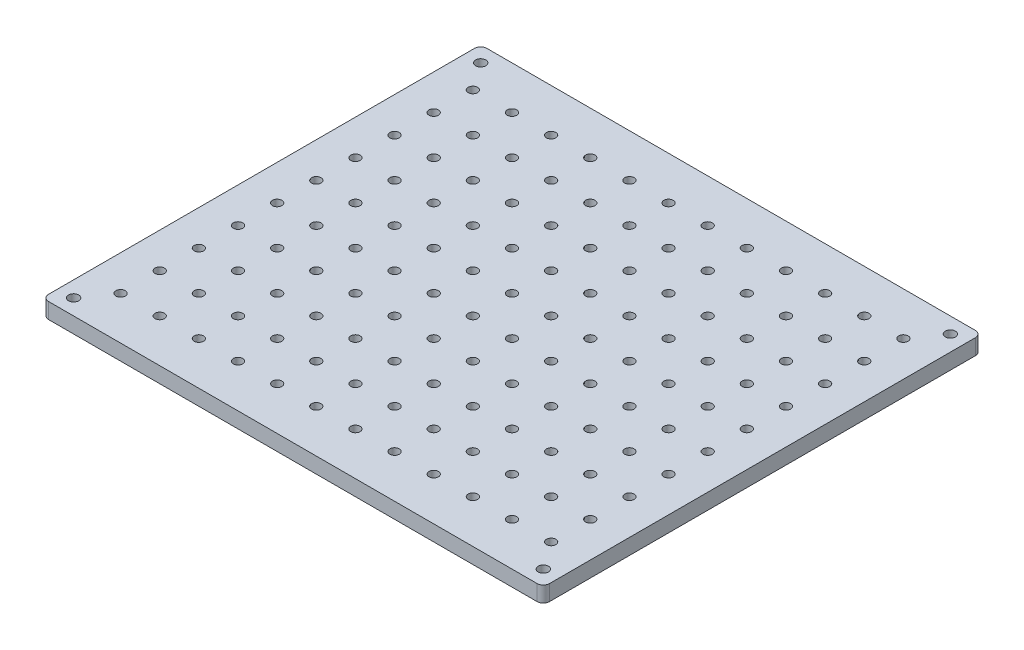
SolidWorks part; units mm, degrees
ref_plane "前视基准面" through (0, 0, 0) normal (0, 0, 1) x (1, 0, 0)
ref_plane "上视基准面" through (0, 0, 0) normal (0, 1, 0) x (1, 0, 0)
ref_plane "右视基准面" through (0, 0, 0) normal (1, 0, 0) x (0, 0, -1)
sketch "草图1" plane through (0, 0, 0) normal (0, 1, 0) x (1, 0, 0)
  line L1 (-160, -140) -> (160, -140)
  line L2 (-160, -140) -> (-160, 140)
  line L3 (-160, 140) -> (160, 140)
  line L4 (160, -140) -> (160, 140)
  line L5 (-160, -140) -> (160, 140) construction
  line L6 (-160, 140) -> (160, -140) construction
  point P0 (0, 0)
extrude "凸台-拉伸1" add sketch "草图1" along normal blind 10
sketch "草图2" plane through (0, 10, 0) normal (0, 1, 0) x (1, 0, 0)
  line L0 (-160, 140) -> (-150, 140)
  line L1 (160, 140) -> (-160, 140) construction
  line L2 (-150, 140) -> (-150, 130)
  line L3 (160, 130) -> (150, 130)
  line L4 (160, -140) -> (160, 140) construction
  line L5 (-150, -140) -> (-150, -130)
  line L6 (-160, -140) -> (160, -140) construction
  circle A0 centre (-150, 130) radius 3.25
  circle A1 centre (-150, 130) radius 2
  circle A2 centre (150, 130) radius 3.25
  circle A3 centre (150, 130) radius 2
  circle A4 centre (-150, -130) radius 3.25
  circle A5 centre (-150, -130) radius 2
  circle A6 centre (150, -130) radius 3.25
  circle A7 centre (150, -130) radius 2
  point P20 (-106.6373, 126.2998)
  point P21 (148.03, 130)
  point P24 (-152.8758, -130)
  point P27 (150, -130)
extrude "切除-拉伸1" cut sketch "草图2" against normal blind 5 contours A6 A7 | A5 A4 | A1 A0 | A3 A2 region at (-147.7669, 10, -132.2331) region at (146.8419, 10, -130) region at (-152.2331, 10, 127.7669) region at (146.8419, 10, 130)
extrude "切除-拉伸2" cut sketch "草图2<3>" against normal through all contours A1 | A3 | A7 | A5 region at (-148.6258, 10, -131.3742) region at (148.0566, 10, -130) region at (-151.3742, 10, 128.6258) region at (150, 10, 130)
sketch "草图2<3>" plane through (0, 10, 0) normal (0, 1, 0) x (1, 0, 0) same geometry as "草图2"
sketch "草图4" plane through (0, 10, 0) normal (0, 1, 0) x (1, 0, 0)
  circle A0 centre (-137.5, 112.5) radius 3
  circle A1 centre (-112.5, 112.5) radius 3
  circle A2 centre (-87.5, 112.5) radius 3
  circle A3 centre (-62.5, 112.5) radius 3
  circle A4 centre (-37.5, 112.5) radius 3
  circle A5 centre (-12.5, 112.5) radius 3
  circle A6 centre (12.5, 112.5) radius 3
  circle A7 centre (37.5, 112.5) radius 3
  circle A8 centre (62.5, 112.5) radius 3
  circle A9 centre (87.5, 112.5) radius 3
  circle A10 centre (112.5, 112.5) radius 3
  circle A11 centre (137.5, 112.5) radius 3
  circle A12 centre (-112.5, 87.5) radius 3
  circle A13 centre (-87.5, 87.5) radius 3
  circle A14 centre (-62.5, 87.5) radius 3
  circle A15 centre (-37.5, 87.5) radius 3
  circle A16 centre (-12.5, 87.5) radius 3
  circle A17 centre (12.5, 87.5) radius 3
  circle A18 centre (37.5, 87.5) radius 3
  circle A19 centre (62.5, 87.5) radius 3
  circle A20 centre (87.5, 87.5) radius 3
  circle A21 centre (112.5, 87.5) radius 3
  circle A22 centre (137.5, 87.5) radius 3
  circle A23 centre (-112.5, 62.5) radius 3
  circle A24 centre (-87.5, 62.5) radius 3
  circle A25 centre (-62.5, 62.5) radius 3
  circle A26 centre (-37.5, 62.5) radius 3
  circle A27 centre (-12.5, 62.5) radius 3
  circle A28 centre (12.5, 62.5) radius 3
  circle A29 centre (37.5, 62.5) radius 3
  circle A30 centre (62.5, 62.5) radius 3
  circle A31 centre (87.5, 62.5) radius 3
  circle A32 centre (112.5, 62.5) radius 3
  circle A33 centre (137.5, 62.5) radius 3
  circle A34 centre (-112.5, 37.5) radius 3
  circle A35 centre (-87.5, 37.5) radius 3
  circle A36 centre (-62.5, 37.5) radius 3
  circle A37 centre (-37.5, 37.5) radius 3
  circle A38 centre (-12.5, 37.5) radius 3
  circle A39 centre (12.5, 37.5) radius 3
  circle A40 centre (37.5, 37.5) radius 3
  circle A41 centre (62.5, 37.5) radius 3
  circle A42 centre (87.5, 37.5) radius 3
  circle A43 centre (112.5, 37.5) radius 3
  circle A44 centre (137.5, 37.5) radius 3
  circle A45 centre (-112.5, 12.5) radius 3
  circle A46 centre (-87.5, 12.5) radius 3
  circle A47 centre (-62.5, 12.5) radius 3
  circle A48 centre (-37.5, 12.5) radius 3
  circle A49 centre (-12.5, 12.5) radius 3
  circle A50 centre (12.5, 12.5) radius 3
  circle A51 centre (37.5, 12.5) radius 3
  circle A52 centre (62.5, 12.5) radius 3
  circle A53 centre (87.5, 12.5) radius 3
  circle A54 centre (112.5, 12.5) radius 3
  circle A55 centre (137.5, 12.5) radius 3
  circle A56 centre (-112.5, -12.5) radius 3
  circle A57 centre (-87.5, -12.5) radius 3
  circle A58 centre (-62.5, -12.5) radius 3
  circle A59 centre (-37.5, -12.5) radius 3
  circle A60 centre (-12.5, -12.5) radius 3
  circle A61 centre (12.5, -12.5) radius 3
  circle A62 centre (37.5, -12.5) radius 3
  circle A63 centre (62.5, -12.5) radius 3
  circle A64 centre (87.5, -12.5) radius 3
  circle A65 centre (112.5, -12.5) radius 3
  circle A66 centre (137.5, -12.5) radius 3
  circle A67 centre (-112.5, -37.5) radius 3
  circle A68 centre (-87.5, -37.5) radius 3
  circle A69 centre (-62.5, -37.5) radius 3
  circle A70 centre (-37.5, -37.5) radius 3
  circle A71 centre (-12.5, -37.5) radius 3
  circle A72 centre (12.5, -37.5) radius 3
  circle A73 centre (37.5, -37.5) radius 3
  circle A74 centre (62.5, -37.5) radius 3
  circle A75 centre (87.5, -37.5) radius 3
  circle A76 centre (112.5, -37.5) radius 3
  circle A77 centre (137.5, -37.5) radius 3
  circle A78 centre (-112.5, -62.5) radius 3
  circle A79 centre (-87.5, -62.5) radius 3
  circle A80 centre (-62.5, -62.5) radius 3
  circle A81 centre (-37.5, -62.5) radius 3
  circle A82 centre (-12.5, -62.5) radius 3
  circle A83 centre (12.5, -62.5) radius 3
  circle A84 centre (37.5, -62.5) radius 3
  circle A85 centre (62.5, -62.5) radius 3
  circle A86 centre (87.5, -62.5) radius 3
  circle A87 centre (112.5, -62.5) radius 3
  circle A88 centre (137.5, -62.5) radius 3
  circle A89 centre (-112.5, -87.5) radius 3
  circle A90 centre (-87.5, -87.5) radius 3
  circle A91 centre (-62.5, -87.5) radius 3
  circle A92 centre (-37.5, -87.5) radius 3
  circle A93 centre (-12.5, -87.5) radius 3
  circle A94 centre (12.5, -87.5) radius 3
  circle A95 centre (37.5, -87.5) radius 3
  circle A96 centre (62.5, -87.5) radius 3
  circle A97 centre (87.5, -87.5) radius 3
  circle A98 centre (112.5, -87.5) radius 3
  circle A99 centre (137.5, -87.5) radius 3
  circle A100 centre (-112.5, -112.5) radius 3
  circle A101 centre (-87.5, -112.5) radius 3
  circle A102 centre (-62.5, -112.5) radius 3
  circle A103 centre (-37.5, -112.5) radius 3
  circle A104 centre (-12.5, -112.5) radius 3
  circle A105 centre (12.5, -112.5) radius 3
  circle A106 centre (37.5, -112.5) radius 3
  circle A107 centre (62.5, -112.5) radius 3
  circle A108 centre (87.5, -112.5) radius 3
  circle A109 centre (112.5, -112.5) radius 3
  circle A110 centre (137.5, -112.5) radius 3
  circle A111 centre (-137.5, 87.5) radius 3
  circle A112 centre (-137.5, 62.5) radius 3
  circle A113 centre (-137.5, 37.5) radius 3
  circle A114 centre (-137.5, 12.5) radius 3
  circle A115 centre (-137.5, -12.5) radius 3
  circle A116 centre (-137.5, -37.5) radius 3
  circle A117 centre (-137.5, -62.5) radius 3
  circle A118 centre (-137.5, -87.5) radius 3
  circle A119 centre (-137.5, -112.5) radius 3
  dimension "D1" = 12
  dimension "D2" = 10
extrude "切除-拉伸3" cut sketch "草图4" against normal through all
fillet "圆角1" radius 4 4 edges at (-160, 5, 140) (160, 5, 140) (160, 5, -140) (-160, 5, -140)
